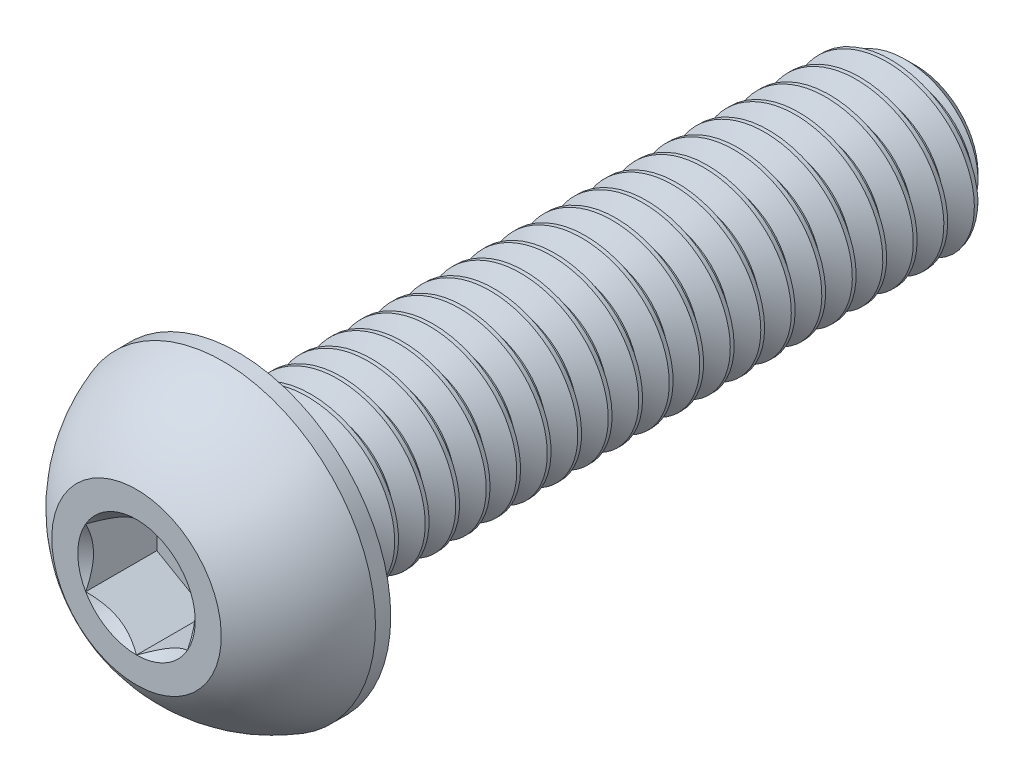
SolidWorks part; units mm, degrees
ref_plane "Front" through (0, 0, 0) normal (0, 0, 1) x (1, 0, 0)
ref_plane "Top" through (0, 0, 0) normal (0, 1, 0) x (1, 0, 0)
ref_plane "Right" through (0, 0, 0) normal (1, 0, 0) x (0, 0, -1)
sketch "Sketch1" plane through (0, 0, 0) normal (1, 0, 0) x (0, 0, -1)
  line L2 (1.5, 1.25) -> (11.5, 1.25)
  line L3 (11.5, 1.25) -> (11.5, 0)
  line L4 (11.5, 0) -> (1.5, 0)
  line L6 (1.275, 2.25) -> (1.5, 2.25) construction
  line L7 (11.5, 1.25) -> (11.5, -1.25) construction
  line L8 (0, 0) -> (1.5, 0) construction
  line L9 (1.5, 2.25) -> (1.5, -2.25) construction
  line L11 (1.5, 1.25) -> (1.5, 0)
  line L13 (0, 0.75) -> (0, -0.75) construction
  line L14 (0, 0.75) -> (0, 1.25) construction
  arc A3 (0, 1.25) -> (1.275, 2.25) centre (2.01, 0) cw construction
  dimension "D1" = 0.225
revolve "Revolve1" add sketch "Sketch1" angle 360 mid plane about L4
sketch "Sketch3" plane through (0, 0, -11.5) normal (0, 0, -1) x (-1, 0, 0)
  circle A0 centre (0, 0) radius 1.25
curve "Helix/Spiral1" pitch 0.45 height 10.45 radius 1.25 centre (0, 0, -11.5) axis (0, 0, 1) start towards (0, 1, 0)
sketch "Sketch2" plane through (0, 0, 0) normal (1, 0, 0) x (0, 0, -1)
  line L0 (11.5, 1.25) -> (11.8937, 1.25)
  line L1 (11.8937, 1.25) -> (11.725, 0.9577)
  line L2 (11.725, 0.9577) -> (11.6687, 0.9577)
  line L3 (11.6687, 0.9577) -> (11.5, 1.25)
  line L4 (11.5844, 1.1039) -> (11.8094, 1.1039) construction
  dimension "D1" = 60
  dimension "D2" = 0.0563
  dimension "D3" = 0.225
chamfer "Chamfer1" distance 0.3375 angle 45 1 edges at (0, 1.25, -11.5)
sweep "Cut-Sweep1" cut profiles "Sketch2" path "Helix/Spiral1" align with end faces yes
sketch "Sketch7" plane through (0, 0, 0) normal (1, 0, 0) x (0, 0, -1)
  line L6 (1.275, 2.25) -> (1.5, 2.25) construction
  line L8 (0, 0) -> (1.5, 0) construction
  line L11 (1.5, 2.25) -> (1.5, -2.25) construction
  line L12 (1.275, 2.25) -> (1.5, 2.25)
  line L13 (0, 0) -> (1.5, 0)
  line L14 (0, 0.75) -> (0, -0.75) construction
  line L15 (1.5, 2.25) -> (1.5, 0)
  line L16 (0, 1.25) -> (0, 0)
  arc A2 (1.275, 2.25) -> (0, 1.25) centre (2.01, 0) ccw construction
  arc A3 (1.275, 2.25) -> (0, 1.25) centre (2.01, 0) ccw
revolve "Revolve2" add sketch "Sketch7" angle 360 mid plane about L13
sketch "Sketch5" plane through (0, 0, 0) normal (0, 0, 1) x (1, 0, 0)
  line L1 (0.75, -0.433) -> (0.75, 0.433)
  line L2 (0.75, 0.433) -> (0, 0.866)
  line L3 (0, 0.866) -> (-0.75, 0.433)
  line L4 (-0.75, 0.433) -> (-0.75, -0.433)
  line L5 (-0.75, -0.433) -> (0, -0.866)
  line L6 (0, -0.866) -> (0.75, -0.433)
  circle A0 centre (0, 0) radius 0.75 construction
extrude "Cut-Extrude2" cut sketch "Sketch5" against normal blind 1.05
sketch "Sketch6" plane through (0, 0, 0) normal (0, 0, 1) x (1, 0, 0)
  circle A0 centre (0, 0) radius 0.866
extrude "Cut-Extrude3" cut sketch "Sketch6" against normal blind 1.05 draft 45
sketch "Sketch9" [suppressed] plane through (0, 0, -4.2164) normal (0, 0, 1) x (1, 0, 0)
  circle A2 centre (0, 0) radius 3.9687
extrude "Boss-Extrude2" [suppressed] add sketch "Sketch9" against normal offset from surface (9.525 mm away) 28.575 up to face at (0, 0.9125, -11.5)
sketch "Sketch10" plane through (0, 0, 0) normal (1, 0, 0) x (0, 0, -1)
  line L0 (11.5, 1.25) -> (11.5, -1.25) construction
  point P0 (10.825, -1.25)
  dimension "D1" = 0.675
equation "\"D3@Helix/Spiral1\" = \"Lg@Sketch1\" + \"D4@Helix/Spiral1\""
equation "\"D2@Sketch2\" = \"D4@Helix/Spiral1\" * .125"
equation "\"D3@Sketch2\" = \"D4@Helix/Spiral1\" * .5"
equation "\"D1@Chamfer1\" = \"D4@Helix/Spiral1\" * .75"
equation "\"D1@Cut-Extrude2\" = \"Head Ht@Sketch1\" * .7"
equation "\"D1@Sketch1\" = \"Head Ht@Sketch1\" * .15"
equation "\"D1@Sketch10\" = \"D4@Helix/Spiral1\" * 1.5"
equation "\"D1@Cut-Extrude3\" = \"D1@Cut-Extrude2\""
